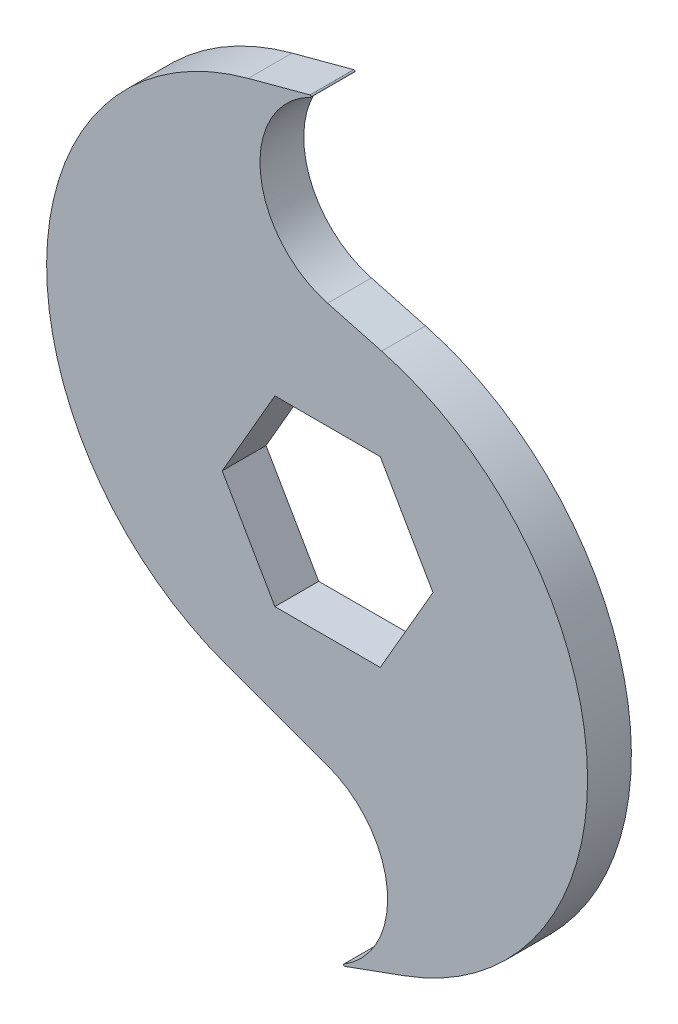
SolidWorks part; units mm, degrees
ref_plane "Front Plane" through (0, 0, 0) normal (0, 0, 1) x (1, 0, 0)
ref_plane "Top Plane" through (0, 0, 0) normal (0, 1, 0) x (1, 0, 0)
ref_plane "Right Plane" through (0, 0, 0) normal (1, 0, 0) x (0, 0, -1)
sketch "Sketch1" plane through (0, 0, 0) normal (0, 0, 1) x (1, 0, 0)
  line L0 (0, 52.07) -> (-11.0405, 49.1117)
  line L1 (0, 52.07) -> (0, 0) construction
  line L2 (0, -52.07) -> (10.7407, -48.1607)
  line L3 (0, 0) -> (0, -52.07) construction
  line L5 (-7.3323, 12.7) -> (-14.6647, 0)
  line L6 (-14.6647, 0) -> (-7.3323, -12.7)
  line L7 (-7.3323, -12.7) -> (7.3323, -12.7)
  line L8 (7.3323, -12.7) -> (14.6647, 0)
  line L9 (14.6647, 0) -> (7.3323, 12.7)
  line L10 (7.3323, 12.7) -> (-7.3323, 12.7)
  line L11 (0, 27.5355) -> (7.5237, 25.5195)
  line L12 (0, -28.2018) -> (-14.1906, -23.0368)
  circle A0 centre (0, 0) radius 52.07 construction
  arc A1 (0, 52.07) -> (0, 27.5355) centre (3.287, 39.8027) ccw
  arc A3 (0, -52.07) -> (0, -28.2018) centre (-4.3437, -40.1359) ccw
  arc A4 (10.7407, -48.1607) -> (7.5237, 25.5195) centre (-2.4834, -11.8278) ccw
  arc A5 (-11.0405, 49.1117) -> (-14.1906, -23.0368) centre (-1.2414, 12.5408) ccw
  circle A6 centre (0, 0) radius 12.7 construction
  dimension "D4" = 70
  dimension "D5" = 25.4
  dimension "D1" = 104.14
  dimension "D6" = 12.7
  dimension "D2" = 11.43
  dimension "D3" = 75
  dimension "D7" = 30
extrude "Boss-Extrude1" add sketch "Sketch1" along normal mid plane 6.096
fillet "Fillet1" radius 0.127 2 edges at (0, 52.07, 0) (0, -52.07, 0)
